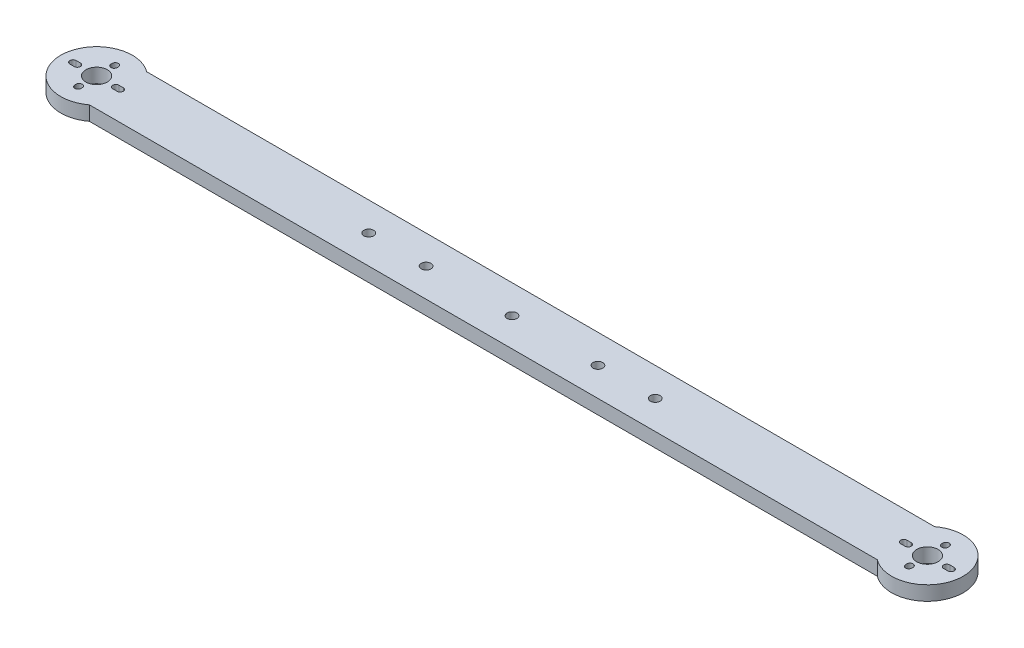
SolidWorks part; units mm, degrees
material "Thornel Mat VMA"
ref_plane "Front Plane" through (0, 0, 0) normal (0, 0, 1) x (1, 0, 0)
ref_plane "Top Plane" through (0, 0, 0) normal (0, 1, 0) x (1, 0, 0)
ref_plane "Right Plane" through (0, 0, 0) normal (1, 0, 0) x (0, 0, -1)
sketch "Sketch1" plane through (0, 0, 0) normal (0, 1, 0) x (1, 0, 0)
  line L0 (0, 12.7) -> (0, -12.7) construction
  line L1 (-174.625, 12.7) -> (174.625, 12.7)
  line L3 (-174.625, -12.7) -> (174.625, -12.7)
  arc A0 (-174.625, 12.7) -> (-174.625, -12.7) centre (-184.15, 0) ccw
  arc A1 (174.625, -12.7) -> (174.625, 12.7) centre (184.15, 0) ccw
  point P8 (0, 12.7)
  point P12 (0, 0)
  dimension "D3" = 31.75
  dimension "D4" = 31.75
extrude "Boss-Extrude1" add sketch "Sketch1" along normal blind 6.35
sketch "Sketch2" plane through (0, 6.35, 0) normal (0, 1, 0) x (1, 0, 0)
  line L0 (173.6914, 0) -> (175.6086, 0) construction
  line L1 (173.6914, 1.375) -> (175.6086, 1.375)
  line L2 (173.6914, -1.375) -> (175.6086, -1.375)
  line L3 (184.15, 0) -> (184.15, 3.2374) construction
  line L4 (194.6086, 0) -> (192.6914, 0) construction
  line L5 (194.6086, 1.375) -> (192.6914, 1.375)
  line L6 (194.6086, -1.375) -> (192.6914, -1.375)
  line L7 (184.15, 8.25) -> (184.15, 7.75) construction
  line L8 (185.525, 8.25) -> (185.525, 7.75)
  line L9 (182.775, 8.25) -> (182.775, 7.75)
  line L10 (184.15, -8.25) -> (184.15, -7.75) construction
  line L11 (185.525, -8.25) -> (185.525, -7.75)
  line L12 (182.775, -8.25) -> (182.775, -7.75)
  line L13 (0, 0) -> (184.15, 0) construction
  line L14 (0, 0) -> (0, 12.7) construction
  line L15 (174.625, 12.7) -> (-174.625, 12.7) construction
  line L16 (-184.15, 0) -> (-184.15, 3.2374) construction
  line L17 (-184.15, -8.25) -> (-184.15, -7.75) construction
  line L18 (-185.525, -8.25) -> (-185.525, -7.75)
  line L19 (-182.775, -8.25) -> (-182.775, -7.75)
  line L20 (-184.15, 8.25) -> (-184.15, 7.75) construction
  line L21 (-185.525, 8.25) -> (-185.525, 7.75)
  line L22 (-182.775, 8.25) -> (-182.775, 7.75)
  line L23 (-194.6086, 0) -> (-192.6914, 0) construction
  line L24 (-194.6086, 1.375) -> (-192.6914, 1.375)
  line L25 (-194.6086, -1.375) -> (-192.6914, -1.375)
  line L26 (-173.6914, 0) -> (-175.6086, 0) construction
  line L27 (-173.6914, 1.375) -> (-175.6086, 1.375)
  line L28 (-173.6914, -1.375) -> (-175.6086, -1.375)
  line L29 (184.15, -8) -> (184.15, 8) construction
  circle A0 centre (184.15, 0) radius 4.75
  arc A1 (173.6914, 1.375) -> (173.6914, -1.375) centre (173.6914, 0) ccw
  arc A2 (175.6086, -1.375) -> (175.6086, 1.375) centre (175.6086, 0) ccw
  arc A3 (194.6086, 1.375) -> (194.6086, -1.375) centre (194.6086, 0) cw
  arc A4 (192.6914, -1.375) -> (192.6914, 1.375) centre (192.6914, 0) cw
  arc A5 (185.525, 8.25) -> (182.775, 8.25) centre (184.15, 8.25) ccw
  arc A6 (182.775, 7.75) -> (185.525, 7.75) centre (184.15, 7.75) ccw
  arc A7 (185.525, -8.25) -> (182.775, -8.25) centre (184.15, -8.25) cw
  arc A8 (182.775, -7.75) -> (185.525, -7.75) centre (184.15, -7.75) cw
  circle A9 centre (-184.15, 0) radius 4.75
  arc A10 (-185.525, -8.25) -> (-182.775, -8.25) centre (-184.15, -8.25) ccw
  arc A11 (-182.775, -7.75) -> (-185.525, -7.75) centre (-184.15, -7.75) ccw
  arc A12 (-185.525, 8.25) -> (-182.775, 8.25) centre (-184.15, 8.25) cw
  arc A13 (-182.775, 7.75) -> (-185.525, 7.75) centre (-184.15, 7.75) cw
  arc A14 (-194.6086, 1.375) -> (-194.6086, -1.375) centre (-194.6086, 0) ccw
  arc A15 (-192.6914, -1.375) -> (-192.6914, 1.375) centre (-192.6914, 0) ccw
  arc A16 (-173.6914, 1.375) -> (-173.6914, -1.375) centre (-173.6914, 0) cw
  arc A17 (-175.6086, -1.375) -> (-175.6086, 1.375) centre (-175.6086, 0) cw
  point P4 (174.65, 0)
  point P12 (193.65, 0)
  point P19 (184.15, 8)
  point P26 (184.15, -8)
  point P41 (-184.15, -8)
  point P48 (-184.15, 8)
  point P55 (-193.65, 0)
  point P62 (-174.65, 0)
  point P69 (184.15, 0)
  dimension "D4" = 9.5
  dimension "D1" = 16
  dimension "D2" = 19
  dimension "D3" = 184.15
  dimension "D5" = 0.5
extrude "Cut-Extrude1" cut sketch "Sketch2" against normal through all
sketch "Sketch3" plane through (0, 6.35, 0) normal (0, 1, 0) x (1, 0, 0)
  circle A0 centre (0, 0) radius 2.159
  circle A1 centre (38.1, 0) radius 2.159
  circle A2 centre (-38.1, 0) radius 2.159
  dimension "D1" = 38.1
  dimension "D3" = 4.318
  dimension "D4" = 4.318
  dimension "D5" = 4.318
  dimension "D2" = 38.1
extrude "Cut-Extrude2" cut sketch "Sketch3" against normal through all
sketch "Sketch4" plane through (0, 6.35, 0) normal (0, 1, 0) x (1, 0, 0)
  line L0 (0, 12.7) -> (0, -33.8789) construction
  line L1 (174.625, 12.7) -> (-174.625, 12.7) construction
  circle A0 centre (63.5, 0) radius 2.159
  circle A1 centre (184.15, 0) radius 4.75 construction
  circle A2 centre (-63.5, 0) radius 2.159
  dimension "D1" = 4.318
  dimension "D2" = 120.65
extrude "Cut-Extrude3" cut sketch "Sketch4" against normal through all
